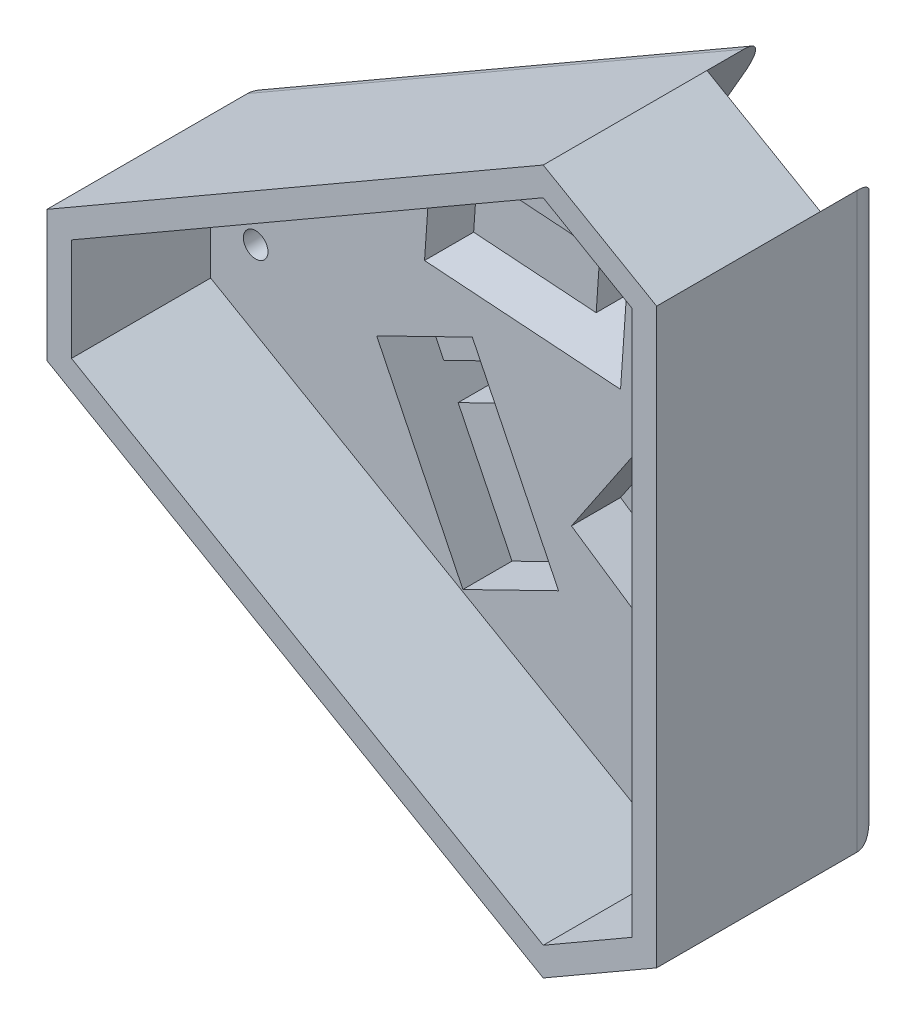
SolidWorks part; units mm, degrees
ref_plane "Plano frontal" through (0, 0, 0) normal (0, 0, 1) x (1, 0, 0)
ref_plane "Plano superior" through (0, 0, 0) normal (0, 1, 0) x (1, 0, 0)
ref_plane "Plano direito" through (0, 0, 0) normal (1, 0, 0) x (0, 0, -1)
sketch "Sketch1" plane through (0, 0, 0) normal (0, 0, 1) x (1, 0, 0)
  line L0 (-45.0333, -8) -> (-45.0333, 8)
  line L1 (-45.0333, 8) -> (15.5885, 43)
  line L2 (15.5885, 43) -> (29.4449, 35)
  line L3 (29.4449, 35) -> (29.4449, -35)
  line L4 (29.4449, -35) -> (15.5885, -43)
  line L5 (15.5885, -43) -> (-45.0333, -8)
  dimension "D1" = 60
  dimension "D2" = 60
  dimension "D3" = 60
  dimension "D4" = 16
  dimension "D5" = 16
  dimension "D6" = 16
  dimension "D7" = 120
  dimension "D8" = 120
  dimension "D9" = 120
  dimension "D10" = 120
  dimension "D11" = 120
  dimension "D12" = 120
  dimension "D13" = 70
  dimension "D14" = 70
  dimension "D15" = 70
extrude "Boss-Extrude1" add sketch "Sketch1" along normal blind 28
sketch "Sketch3" plane through (22.5167, 39, 0) normal (0.5, 0.866, 0) x (0.866, -0.5, 0)
  line L1 (8, -28) -> (8, 0) construction
  line L2 (-8, 0) -> (8, 0)
  line L3 (-8, 0) -> (-8, -8)
  line L4 (-8, -8) -> (8, -8)
  line L6 (8, 0) -> (8, -8)
  dimension "D1" = 8
extrude "Cut-Extrude1" cut sketch "Sketch3" against normal blind 12
sketch "Sketch4" plane through (-45.0333, 0, 0) normal (-1, 0, 0) x (0, 0, 1)
  line L0 (28, 8) -> (0, 8) construction
  line L1 (0, -8) -> (8, -8)
  line L2 (0, -8) -> (0, 8)
  line L3 (0, 8) -> (8, 8)
  line L4 (8, -8) -> (8, 8)
  dimension "D1" = 8
extrude "Cut-Extrude2" cut sketch "Sketch4" against normal blind 12
sketch "Sketch5" plane through (22.5167, -39, 0) normal (0.5, -0.866, 0) x (0.866, 0.5, 0)
  line L0 (8, 28) -> (8, 0) construction
  line L1 (-8, 0) -> (8, 0)
  line L2 (-8, 0) -> (-8, 8)
  line L3 (-8, 8) -> (8, 8)
  line L4 (8, 0) -> (8, 8)
  dimension "D1" = 8
extrude "Cut-Extrude3" cut sketch "Sketch5" against normal blind 12
sketch "Sketch6" plane through (0, 0, 8) normal (0, 0, -1) x (-1, 0, 0)
  line L0 (45.0333, -8) -> (45.0333, 8) construction
  line L1 (-15.5885, 43) -> (-29.4449, 35) construction
  line L2 (-29.4449, -35) -> (-15.5885, -43) construction
  line L3 (-23.4449, 24.6077) -> (-29.4449, 35) construction
  line L5 (33.0333, 8) -> (45.0333, 8) construction
  line L6 (-23.4449, -24.6077) -> (-29.4449, -35) construction
  circle A0 centre (-18.2667, -31.6388) radius 1.5
  circle A1 centre (-18.2667, 31.6388) radius 1.5
  circle A2 centre (36.5333, 0) radius 1.5
  point P10 (-22.5167, 39)
  dimension "D1" = 8.5
  dimension "D2" = 3
  dimension "D3" = 3
  dimension "D4" = 8.5
  dimension "D5" = 8.5
  dimension "D6" = 3
  dimension "D7" = 8
  dimension "D8" = 8
  dimension "D9" = 8
extrude "Cut-Extrude4" cut sketch "Sketch6" against normal through all
sketch "Sketch7" plane through (0, 0, 28) normal (0, 0, 1) x (1, 0, 0)
  line L0 (-42.0333, -6.2679) -> (-42.0333, 6.2679)
  line L1 (-42.0333, 6.2679) -> (15.5885, 39.5359)
  line L2 (15.5885, 39.5359) -> (26.4449, 33.2679)
  line L3 (26.4449, 33.2679) -> (26.4449, -33.2679)
  line L4 (26.4449, -33.2679) -> (15.5885, -39.5359)
  line L5 (15.5885, -39.5359) -> (-42.0333, -6.2679)
  line L6 (-45.0333, 8) -> (-45.0333, -8) construction
  line L7 (-45.0333, -8) -> (15.5885, -43) construction
  line L8 (15.5885, 43) -> (-45.0333, 8) construction
  line L9 (29.4449, 35) -> (15.5885, 43) construction
  line L10 (29.4449, -35) -> (29.4449, 35) construction
  line L11 (15.5885, -43) -> (29.4449, -35) construction
  dimension "D1" = 3
  dimension "D2" = 3
  dimension "D3" = 3
  dimension "D4" = 3
  dimension "D5" = 3
  dimension "D6" = 3
extrude "Cut-Extrude5" cut sketch "Sketch7" against normal blind 17
sketch "Sketch8" plane through (0, 0, 11) normal (0, 0, 1) x (1, 0, 0)
  line L0 (-11.2188, -23.8058) -> (-21.7508, -2.2402)
  line L1 (-21.7508, -2.2402) -> (-10.0695, 3.4647)
  line L2 (-10.0695, 3.4647) -> (0.4626, -18.1009)
  line L3 (0.4626, -18.1009) -> (-11.2188, -23.8058)
  circle A0 centre (-36.5333, 0) radius 1.5 construction
  dimension "D1" = 24
  dimension "D2" = 13
  dimension "D3" = 8.5
  dimension "D4" = 12.3
extrude "Cut-Extrude6" cut sketch "Sketch8" against normal blind 6
sketch "Sketch9" plane through (0, 0, 5) normal (0, 0, 1) x (1, 0, 0)
  line L0 (-19.5567, -6.733) -> (-7.8753, -1.0281)
  line L1 (-21.7508, -2.2402) -> (-11.2188, -23.8058) construction
  line L2 (0.4626, -18.1009) -> (-10.0695, 3.4647) construction
  line L3 (-7.8753, -1.0281) -> (-6.1199, -4.6224)
  line L4 (-6.1199, -4.6224) -> (-17.8013, -10.3273)
  line L5 (-17.8013, -10.3273) -> (-19.5567, -6.733)
  line L7 (-11.2188, -23.8058) -> (0.4626, -18.1009) construction
  dimension "D1" = 15
  dimension "D2" = 4
extrude "Cut-Extrude7" cut sketch "Sketch9" against normal through all
sketch "Sketch10" plane through (0, 0, 0) normal (0, 1, 0) x (1, 0, 0)
  line L0 (0, 0) -> (0, -36.7235) construction
ref_axis "Axis1" through (0, 0, 0) along (0, 0, 1)
pattern_circular "CirPattern1" count 3 over 360 about axis through (0, 0, 0) along (0, 0, 1) of "Cut-Extrude6", "Cut-Extrude7"
sketch "Sketch11" plane through (-33.0333, 0, 0) normal (-1, 0, 0) x (0, 0, 1)
  line L0 (8, -8) -> (8, 8) construction
  line L1 (8, -8) -> (8, 8) construction
  line L2 (0, -8) -> (8, -8) construction
  line L3 (28, 8) -> (8, 8) construction
  circle A0 centre (4.5, 4.25) radius 1
  circle A1 centre (4.5, -4.25) radius 1
  dimension "D1" = 3.5
  dimension "D2" = 3.5
  dimension "D3" = 8.5
  dimension "D4" = 3.75
  dimension "D5" = 3.75
  dimension "D6" = 2
  dimension "D7" = 2
extrude "Cut-Extrude8" cut sketch "Sketch11" against normal blind 10
pattern_circular "CirPattern2" count 3 over 360 about axis through (0, 0, 0) along (0, 0, 1) of "Cut-Extrude8"
fillet "Fillet1" radius 3.5 3 edges at (-14.7224, -25.5, 0) (-14.7224, 25.5, 0) (29.4449, 0, 0)
